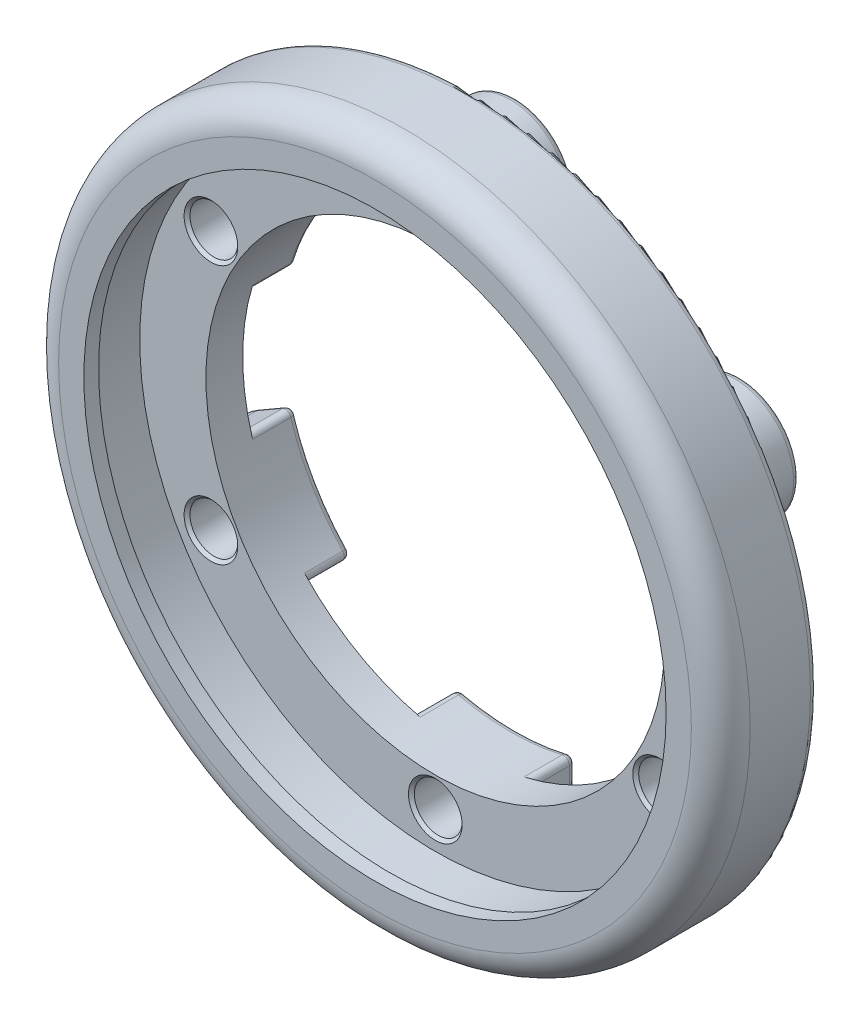
SolidWorks part; units mm, degrees
ref_plane "前视基准面" through (0, 0, 0) normal (0, 0, 1) x (1, 0, 0)
ref_plane "上视基准面" through (0, 0, 0) normal (0, 1, 0) x (1, 0, 0)
ref_plane "右视基准面" through (0, 0, 0) normal (1, 0, 0) x (0, 0, -1)
sketch "草图1" plane through (0, 0, 0) normal (0, 0, 1) x (1, 0, 0)
  circle A20 centre (0, 0) radius 23.5157 construction
  circle A21 centre (0, 0) radius 23.5157
  circle A22 centre (0, 0) radius 15.6 construction
  circle A23 centre (0, 0) radius 15.6
extrude "凸台-拉伸1" add sketch "草图1" along normal blind 3.5
sketch "草图2" plane through (0, 0, 0) normal (0, 0, -1) x (-1, 0, 0)
  circle A0 centre (0.0014, 17.6178) radius 1.625
  circle A1 centre (15.2581, 8.8077) radius 1.625
  circle A2 centre (15.2567, -8.8101) radius 1.625
  circle A3 centre (-0.0014, -17.6178) radius 1.625
  circle A4 centre (-15.2581, -8.8077) radius 1.625
  circle A5 centre (-15.2567, 8.8101) radius 1.625
  point P15 (0, 0)
  dimension "D1" = 3.25
extrude "切除-拉伸1" cut sketch "草图2" against normal blind 10.2
sketch "草图3" plane through (0, 0, 3.5) normal (0, 0, 1) x (1, 0, 0)
  circle A0 centre (0, 0) radius 20.1
  dimension "D1" = 40.2
extrude "切除-拉伸2" cut sketch "草图3" against normal blind 1
fillet "圆角3" radius 0.5 1 edges at (23.5157, 0, 0)
sketch "草图6" plane through (0, 0, 3.5) normal (0, 0, 1) x (1, 0, 0)
  circle A0 centre (0, 0) radius 20.1 construction
  circle A1 centre (0, 0) radius 23.5157
  circle A2 centre (0, 0) radius 23.5157
  circle A3 centre (0, 0) radius 20.1
  dimension "D1" = 0
extrude "凸台-拉伸2" add sketch "草图6" along normal blind 3.1
sketch "草图7" plane through (0, 0, 6.6) normal (0, 0, 1) x (1, 0, 0)
  circle A1 centre (0, 0) radius 23.5157
  circle A2 centre (0, 0) radius 23.5157
  circle A4 centre (0, 0) radius 19.8
  circle A5 centre (0, 0) radius 19.8
  dimension "D1" = 0
  dimension "D2" = 0.3
extrude "凸台-拉伸3" add sketch "草图7" against normal blind 1
fillet "圆角4" radius 2 1 edges at (23.5157, 0, 6.6)
sketch "草图8" plane through (0, 0, 0) normal (0, 0, -1) x (-1, 0, 0)
  line L0 (-2.0164, 17.6178) -> (-2.0164, 15.4691)
  line L1 (2.0192, 17.6178) -> (2.0192, 15.4688)
  line L2 (14.2493, 10.5551) -> (12.3885, 9.4808)
  line L3 (16.267, 7.0602) -> (14.4059, 5.9857)
  line L4 (16.2656, -7.0627) -> (14.4048, -5.9884)
  line L5 (14.2478, -10.5575) -> (12.3868, -9.483)
  line L6 (2.0164, -17.6178) -> (2.0164, -15.4691)
  line L7 (-2.0192, -17.6178) -> (-2.0192, -15.4688)
  line L8 (-14.2493, -10.5551) -> (-12.3885, -9.4808)
  line L9 (-16.267, -7.0602) -> (-14.4059, -5.9857)
  line L10 (-16.2656, 7.0627) -> (-14.4048, 5.9884)
  line L11 (-14.2478, 10.5575) -> (-12.3868, 9.483)
  circle A0 centre (0, 0) radius 15.6 construction
  arc A1 (2.0192, 15.4688) -> (-2.0164, 15.4691) centre (0, 0) ccw
  arc A2 (2.0192, 17.6178) -> (-2.0164, 17.6178) centre (0.0014, 17.6178) ccw
  circle A3 centre (0.0014, 17.6178) radius 1.55
  arc A4 (14.4059, 5.9857) -> (12.3885, 9.4808) centre (0, 0) ccw
  arc A5 (16.267, 7.0602) -> (14.2493, 10.5551) centre (15.2581, 8.8077) ccw
  circle A6 centre (15.2581, 8.8077) radius 1.55
  arc A7 (12.3868, -9.483) -> (14.4048, -5.9884) centre (0, 0) ccw
  arc A8 (14.2478, -10.5575) -> (16.2656, -7.0627) centre (15.2567, -8.8101) ccw
  circle A9 centre (15.2567, -8.8101) radius 1.55
  arc A10 (-2.0192, -15.4688) -> (2.0164, -15.4691) centre (0, 0) ccw
  arc A11 (-2.0192, -17.6178) -> (2.0164, -17.6178) centre (-0.0014, -17.6178) ccw
  circle A12 centre (-0.0014, -17.6178) radius 1.55
  arc A13 (-14.4059, -5.9857) -> (-12.3885, -9.4808) centre (0, 0) ccw
  arc A14 (-16.267, -7.0602) -> (-14.2493, -10.5551) centre (-15.2581, -8.8077) ccw
  circle A15 centre (-15.2581, -8.8077) radius 1.55
  arc A16 (-12.3868, 9.483) -> (-14.4048, 5.9884) centre (0, 0) ccw
  arc A17 (-14.2478, 10.5575) -> (-16.2656, 7.0627) centre (-15.2567, 8.8101) ccw
  circle A18 centre (-15.2567, 8.8101) radius 1.55
  point P41 (0, 0)
  dimension "D1" = 6
extrude "凸台-拉伸4" add sketch "草图8" along normal blind 3
sketch "草图9" plane through (0, 0, -3) normal (0, 0, -1) x (-1, 0, 0)
  line L2 (-14.2493, -10.5551) -> (-12.3885, -9.4808)
  line L3 (-14.4059, -5.9857) -> (-16.267, -7.0602)
  line L4 (-14.2493, -10.5551) -> (-12.3885, -9.4808)
  line L5 (-14.4059, -5.9857) -> (-16.267, -7.0602)
  line L6 (-16.2656, 7.0627) -> (-14.4048, 5.9884)
  line L7 (-12.3868, 9.483) -> (-14.2478, 10.5575)
  line L8 (-16.2656, 7.0627) -> (-14.4048, 5.9884)
  line L9 (-12.3868, 9.483) -> (-14.2478, 10.5575)
  line L10 (-2.0164, 17.6178) -> (-2.0164, 15.4691)
  line L11 (2.0192, 15.4688) -> (2.0192, 17.6178)
  line L12 (-2.0164, 17.6178) -> (-2.0164, 15.4691)
  line L13 (2.0192, 15.4688) -> (2.0192, 17.6178)
  line L14 (2.0164, -17.6178) -> (2.0164, -15.4691)
  line L15 (-2.0192, -15.4688) -> (-2.0192, -17.6178)
  line L16 (2.0164, -17.6178) -> (2.0164, -15.4691)
  line L17 (-2.0192, -15.4688) -> (-2.0192, -17.6178)
  line L18 (16.2656, -7.0627) -> (14.4048, -5.9884)
  line L19 (12.3868, -9.483) -> (14.2478, -10.5575)
  line L20 (16.2656, -7.0627) -> (14.4048, -5.9884)
  line L21 (12.3868, -9.483) -> (14.2478, -10.5575)
  line L22 (14.2493, 10.5551) -> (12.3885, 9.4808)
  line L23 (14.4059, 5.9857) -> (16.267, 7.0602)
  line L24 (14.2493, 10.5551) -> (12.3885, 9.4808)
  line L25 (14.4059, 5.9857) -> (16.267, 7.0602)
  arc A2 (-16.267, -7.0602) -> (-14.2493, -10.5551) centre (-15.2581, -8.8077) ccw
  arc A3 (-14.4059, -5.9857) -> (-12.3885, -9.4808) centre (0, 0) ccw
  arc A4 (-16.267, -7.0602) -> (-14.2493, -10.5551) centre (-15.2581, -8.8077) ccw
  arc A5 (-14.4059, -5.9857) -> (-12.3885, -9.4808) centre (0, 0) ccw
  arc A6 (-14.2478, 10.5575) -> (-16.2656, 7.0627) centre (-15.2567, 8.8101) ccw
  arc A7 (-12.3868, 9.483) -> (-14.4048, 5.9884) centre (0, 0) ccw
  arc A8 (-14.2478, 10.5575) -> (-16.2656, 7.0627) centre (-15.2567, 8.8101) ccw
  arc A9 (-12.3868, 9.483) -> (-14.4048, 5.9884) centre (0, 0) ccw
  arc A10 (2.0192, 17.6178) -> (-2.0164, 17.6178) centre (0.0014, 17.6178) ccw
  arc A11 (2.0192, 15.4688) -> (-2.0164, 15.4691) centre (0, 0) ccw
  arc A12 (2.0192, 17.6178) -> (-2.0164, 17.6178) centre (0.0014, 17.6178) ccw
  arc A13 (2.0192, 15.4688) -> (-2.0164, 15.4691) centre (0, 0) ccw
  arc A14 (-2.0192, -17.6178) -> (2.0164, -17.6178) centre (-0.0014, -17.6178) ccw
  arc A15 (-2.0192, -15.4688) -> (2.0164, -15.4691) centre (0, 0) ccw
  arc A16 (-2.0192, -17.6178) -> (2.0164, -17.6178) centre (-0.0014, -17.6178) ccw
  arc A17 (-2.0192, -15.4688) -> (2.0164, -15.4691) centre (0, 0) ccw
  arc A18 (14.2478, -10.5575) -> (16.2656, -7.0627) centre (15.2567, -8.8101) ccw
  arc A19 (12.3868, -9.483) -> (14.4048, -5.9884) centre (0, 0) ccw
  arc A20 (14.2478, -10.5575) -> (16.2656, -7.0627) centre (15.2567, -8.8101) ccw
  arc A21 (12.3868, -9.483) -> (14.4048, -5.9884) centre (0, 0) ccw
  arc A22 (16.267, 7.0602) -> (14.2493, 10.5551) centre (15.2581, 8.8077) ccw
  arc A23 (14.4059, 5.9857) -> (12.3885, 9.4808) centre (0, 0) ccw
  arc A24 (16.267, 7.0602) -> (14.2493, 10.5551) centre (15.2581, 8.8077) ccw
  arc A25 (14.4059, 5.9857) -> (12.3885, 9.4808) centre (0, 0) ccw
  dimension "D1" = 0
  dimension "D2" = 0
  dimension "D3" = 0
  dimension "D4" = 0
  dimension "D5" = 0
  dimension "D6" = 0
extrude "凸台-拉伸5" add sketch "草图9" against normal blind 1
chamfer "倒角1" distance 0.2 angle 45 6 edges at (16.8831, -8.8077, 2.5) (16.8817, 8.8101, 2.5) (1.6236, 17.6178, 2.5) (-13.6331, 8.8077, 2.5) (1.6264, -17.6178, 2.5) (-13.6317, -8.8101, 2.5)
sketch "草图10" plane through (0, 0, -3) normal (0, 0, -1) x (-1, 0, 0)
  line L0 (4.0164, -17.6178) -> (4.0164, -15.0741)
  line L1 (-4.0192, -15.0734) -> (-4.0192, -17.6178)
  line L2 (16.2656, -7.0627) -> (14.4048, -5.9884)
  line L3 (12.3868, -9.483) -> (14.2478, -10.5575)
  line L4 (17.2656, -5.3306) -> (13.2608, -3.0184)
  line L5 (9.2423, -9.977) -> (13.2478, -12.2896)
  line L6 (17.2656, -5.3306) -> (15.0627, -4.0588)
  line L7 (11.0443, -11.0174) -> (13.2478, -12.2896)
  line L8 (16.2656, -7.0627) -> (14.4048, -5.9884)
  line L9 (12.3868, -9.483) -> (14.2478, -10.5575)
  line L10 (2.0164, -17.6178) -> (2.0164, -15.4691)
  line L11 (-2.0192, -15.4688) -> (-2.0192, -17.6178)
  line L12 (-13.2493, -12.2871) -> (-11.0464, -11.0153)
  line L13 (-15.0635, -4.056) -> (-17.267, -5.3282)
  line L14 (-14.2493, -10.5551) -> (-12.3885, -9.4808)
  line L15 (-14.4059, -5.9857) -> (-16.267, -7.0602)
  line L16 (-17.2656, 5.3306) -> (-15.0627, 4.0588)
  line L17 (-11.0443, 11.0174) -> (-13.2478, 12.2896)
  line L18 (-16.2656, 7.0627) -> (-14.4048, 5.9884)
  line L19 (-12.3868, 9.483) -> (-14.2478, 10.5575)
  line L20 (-4.0164, 17.6178) -> (-4.0164, 15.0741)
  line L21 (4.0192, 15.0734) -> (4.0192, 17.6178)
  line L22 (-2.0164, 17.6178) -> (-2.0164, 15.4691)
  line L23 (2.0192, 15.4688) -> (2.0192, 17.6178)
  line L24 (13.2493, 12.2871) -> (11.0464, 11.0153)
  line L25 (15.0635, 4.056) -> (17.267, 5.3282)
  line L26 (14.2493, 10.5551) -> (12.3885, 9.4808)
  line L27 (14.4059, 5.9857) -> (16.267, 7.0602)
  arc A0 (14.4048, -5.9884) -> (15.0627, -4.0588) centre (0, 0) ccw
  arc A1 (2.0164, -15.4691) -> (4.0164, -15.0741) centre (0, 0) ccw
  arc A2 (11.0443, -11.0174) -> (12.3868, -9.483) centre (0, 0) ccw
  arc A3 (14.2478, -10.5575) -> (16.2656, -7.0627) centre (15.2567, -8.8101) ccw
  arc A4 (13.2478, -12.2896) -> (17.2656, -5.3306) centre (15.2567, -8.8101) ccw
  arc A5 (9.2423, -9.977) -> (13.2608, -3.0184) centre (0, 0) ccw
  arc A6 (13.2478, -12.2896) -> (17.2656, -5.3306) centre (15.2567, -8.8101) ccw
  arc A7 (12.3868, -9.483) -> (14.4048, -5.9884) centre (0, 0) ccw
  arc A8 (14.2478, -10.5575) -> (16.2656, -7.0627) centre (15.2567, -8.8101) ccw
  arc A10 (-4.0192, -15.0734) -> (-2.0192, -15.4688) centre (0, 0) ccw
  arc A11 (-4.0192, -17.6178) -> (4.0164, -17.6178) centre (-0.0014, -17.6178) ccw
  arc A12 (-2.0192, -17.6178) -> (2.0164, -17.6178) centre (-0.0014, -17.6178) ccw
  arc A13 (-12.3885, -9.4808) -> (-11.0464, -11.0153) centre (0, 0) ccw
  arc A14 (-15.0635, -4.056) -> (-14.4059, -5.9857) centre (0, 0) ccw
  arc A15 (-17.267, -5.3282) -> (-13.2493, -12.2871) centre (-15.2581, -8.8077) ccw
  arc A16 (-16.267, -7.0602) -> (-14.2493, -10.5551) centre (-15.2581, -8.8077) ccw
  arc A17 (-14.4048, 5.9884) -> (-15.0627, 4.0588) centre (0, 0) ccw
  arc A18 (-11.0443, 11.0174) -> (-12.3868, 9.483) centre (0, 0) ccw
  arc A19 (-13.2478, 12.2896) -> (-17.2656, 5.3306) centre (-15.2567, 8.8101) ccw
  arc A20 (-14.2478, 10.5575) -> (-16.2656, 7.0627) centre (-15.2567, 8.8101) ccw
  arc A21 (-2.0164, 15.4691) -> (-4.0164, 15.0741) centre (0, 0) ccw
  arc A22 (4.0192, 15.0734) -> (2.0192, 15.4688) centre (0, 0) ccw
  arc A23 (4.0192, 17.6178) -> (-4.0164, 17.6178) centre (0.0014, 17.6178) ccw
  arc A24 (2.0192, 17.6178) -> (-2.0164, 17.6178) centre (0.0014, 17.6178) ccw
  arc A25 (12.3885, 9.4808) -> (11.0464, 11.0153) centre (0, 0) ccw
  arc A26 (15.0635, 4.056) -> (14.4059, 5.9857) centre (0, 0) ccw
  arc A27 (17.267, 5.3282) -> (13.2493, 12.2871) centre (15.2581, 8.8077) ccw
  arc A28 (16.267, 7.0602) -> (14.2493, 10.5551) centre (15.2581, 8.8077) ccw
  point P68 (0, 0)
  dimension "D1" = 2
  dimension "D2" = 0
  dimension "D3" = 6
extrude "凸台-拉伸6" add sketch "草图10" against normal up to surface (3 mm away) up to face at (23.0157, 0, 0)
fillet "圆角5" radius 0.4 36 edges at (18.7376, -10.8165, -3) (16.1653, -4.6921, -3) (13.5107, -7.7987, -3) (12.1478, -11.6512, -3) (-0.0014, 21.6355, -3) (-4.0192, 16.3456, -3) (-0.0015, 15.6, -3) (4.0164, 16.3459, -3) (18.7362, 10.819, -3) (12.1461, 11.6535, -3) (13.5093, 7.8013, -3) (16.1642, 4.6947, -3) (0.0014, -21.6355, -3) (4.0192, -16.3456, -3) (0.0015, -15.6, -3) (-4.0164, -16.3459, -3) (-18.7362, -10.819, -3) (-12.1461, -11.6535, -3) (-13.5093, -7.8013, -3) (-16.1642, -4.6947, -3) (-18.7376, 10.8165, -3) (-16.1653, 4.6921, -3) (-13.5107, 7.7987, -3) (-12.1478, 11.6512, -3) (-4.0164, -15.0741, -1.5) (4.0192, -15.0734, -1.5) (-11.0443, -11.0174, -1.5) (-15.0627, -4.0588, -1.5) (-15.0635, 4.056, -1.5) (-11.0464, 11.0153, -1.5) (-4.0192, 15.0734, -1.5) (4.0164, 15.0741, -1.5) (11.0443, 11.0174, -1.5) (15.0627, 4.0588, -1.5) (15.0635, -4.056, -1.5) (11.0464, -11.0153, -1.5)
